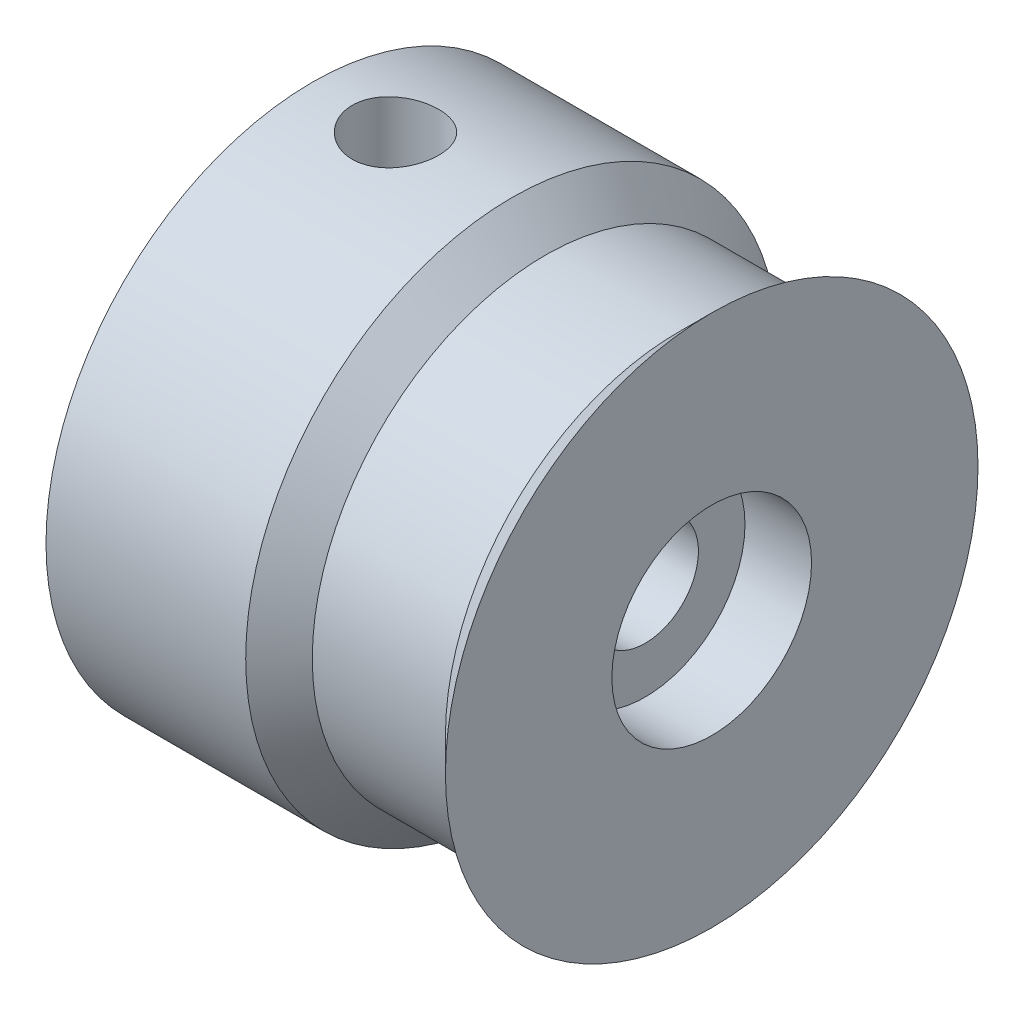
SolidWorks part; units mm, degrees
ref_plane "Front Plane" through (0, 0, 0) normal (0, 0, 1) x (1, 0, 0)
ref_plane "Top Plane" through (0, 0, 0) normal (0, 1, 0) x (1, 0, 0)
ref_plane "Right Plane" through (0, 0, 0) normal (1, 0, 0) x (0, 0, -1)
sketch "Sketch1" plane through (0, 0, 0) normal (0, 0, 1) x (1, 0, 0)
  line L0 (0, 0) -> (34.197, 0) construction
  line L1 (0, 4.5) -> (0, 8)
  line L2 (0, 8) -> (7, 8)
  line L7 (7, 8) -> (7, 7)
  line L8 (7, 7) -> (11, 7)
  line L9 (11, 7) -> (11, 8)
  line L10 (11, 8) -> (12, 8)
  line L11 (12, 8) -> (12, 3)
  line L12 (12, 3) -> (10, 3)
  line L13 (10, 3) -> (10, 1.6)
  line L14 (10, 1.6) -> (5, 1.6)
  line L16 (5, 4.5) -> (0, 4.5)
  line L18 (5, 4.5) -> (5, 1.6)
  dimension "D1" = 12
  dimension "D2" = 4
  dimension "D3" = 1
  dimension "D5" = 1
  dimension "D6" = 4.5
  dimension "D7" = 7
  dimension "D8" = 2
  dimension "D9" = 3
  dimension "D10" = 1.6
  dimension "D11" = 5
  dimension "D14" = 8
revolve "Revolve1" add sketch "Sketch1" angle 360 about L0
sketch "Sketch2" plane through (0, 0, 0) normal (0, 1, 0) x (1, 0, 0)
  line L0 (0, 8) -> (0, -8) construction
  line L1 (0, 0) -> (2.5, 0) construction
  circle A0 centre (2.5, 0) radius 1.3
  dimension "D1" = 2.6
  dimension "D2" = 2.5
extrude "Cut-Extrude1" cut sketch "Sketch2" against normal through all both and the other way through all
chamfer "Chamfer1" distance 1 angle 45 2 edges at (11, 0, 8) (7, 0, 8)
